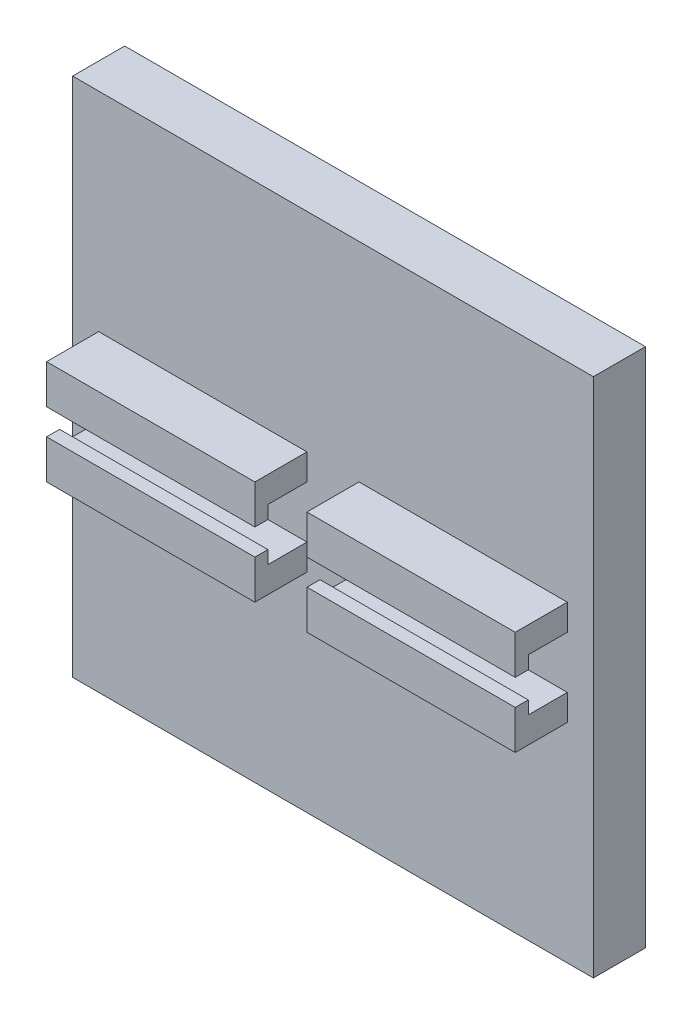
SolidWorks part; units mm, degrees
ref_plane "Front Plane" through (0, 0, 0) normal (0, 0, 1) x (1, 0, 0)
ref_plane "Top Plane" through (0, 0, 0) normal (0, 1, 0) x (1, 0, 0)
ref_plane "Right Plane" through (0, 0, 0) normal (1, 0, 0) x (0, 0, -1)
sketch "Sketch1" plane through (0, 0, 0) normal (0, 0, 1) x (1, 0, 0)
  line L1 (-50, 50) -> (50, 50)
  line L2 (-50, 50) -> (-50, -50)
  line L3 (-50, -50) -> (50, -50)
  line L4 (50, 50) -> (50, -50)
  line L5 (-50, 50) -> (50, -50) construction
  line L6 (-50, -50) -> (50, 50) construction
  point P0 (0, 0)
  dimension "D1" = 100
  dimension "D2" = 100
extrude "back plate" add sketch "Sketch1" along normal blind 10
sketch "Sketch2" plane through (0, 0, 10) normal (0, 0, 1) x (1, 0, 0)
  line L0 (-25, 0) -> (-25, 50) construction
  line L1 (-50, 50) -> (-50, -50) construction
  line L3 (-50, 0) -> (0, 0) construction
  line L4 (-45, 10) -> (-5, 10)
  line L5 (-45, 10) -> (-45, -10)
  line L6 (-45, -10) -> (-5, -10)
  line L7 (-5, 10) -> (-5, -10)
  line L8 (-45, 10) -> (-5, -10) construction
  line L9 (-45, -10) -> (-5, 10) construction
  line L12 (50, 50) -> (-50, 50) construction
  point P6 (-25, 0)
  point P13 (0, 0)
  dimension "D1" = 20
  dimension "D2" = 40
extrude "slider mount boss" add sketch "Sketch2" along normal blind 10
sketch "Sketch3" plane through (-5, 0, 0) normal (1, 0, 0) x (0, 0, -1)
  line L0 (-10, -10) -> (-10, 10) construction
  line L1 (-17.5, 5) -> (-10, 5)
  line L2 (-17.5, 5) -> (-17.5, 2.5)
  line L3 (-17.5, -5) -> (-10, -5)
  line L4 (-10, 5) -> (-10, -5)
  line L5 (-17.5, 5) -> (-10, -5) construction
  line L6 (-17.5, -5) -> (-10, 5) construction
  line L7 (-17.5, -2.5) -> (-17.5, -5)
  line L8 (-20, 2.5) -> (-17.5, 2.5)
  line L9 (-20, 2.5) -> (-20, -2.5)
  line L10 (-20, -2.5) -> (-17.5, -2.5)
  line L12 (-20, 2.5) -> (-17.5, -2.5) construction
  line L13 (-20, -2.5) -> (-17.5, 2.5) construction
  point P4 (-13.75, 0)
  point P6 (-10, 0)
  point P12 (-18.75, 0)
  point P14 (-17.5, 0)
  dimension "D1" = 7.5
  dimension "D2" = 10
  dimension "D3" = 5
  dimension "D4" = 2.5
extrude "slider mount" cut sketch "Sketch3" against normal through all
mirror "Mirror3" about plane through (0, 0, 0) normal (1, 0, 0) of "slider mount", "slider mount boss"
